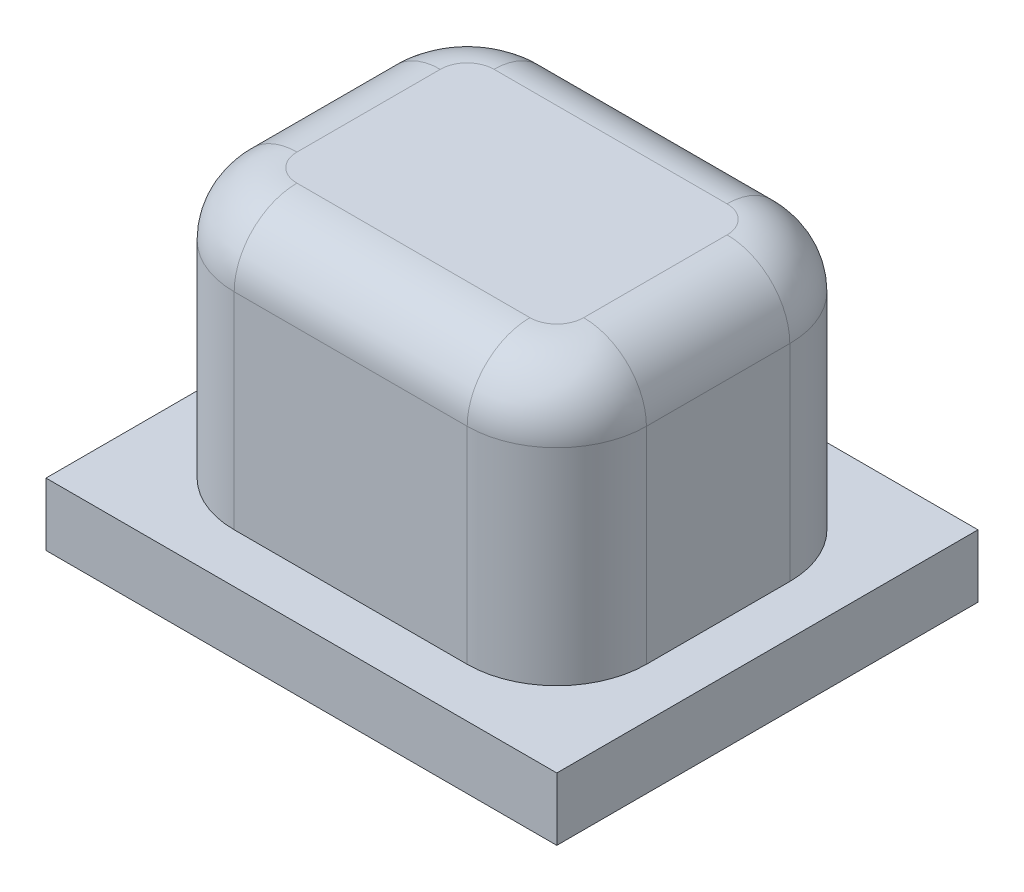
SolidWorks part; units mm, degrees
ref_plane "前视基准面" through (0, 0, 0) normal (0, 0, 1) x (1, 0, 0)
ref_plane "上视基准面" through (0, 0, 0) normal (0, 1, 0) x (1, 0, 0)
ref_plane "右视基准面" through (0, 0, 0) normal (1, 0, 0) x (0, 0, -1)
sketch "草图1" plane through (0, 0, 0) normal (0, 1, 0) x (1, 0, 0)
  line L1 (-1.3, -1.8) -> (1.3, -1.8)
  line L2 (-2.3, -0.8) -> (-2.3, 0.8)
  line L3 (-1.3, 1.8) -> (1.3, 1.8)
  line L4 (2.3, -0.8) -> (2.3, 0.8)
  line L5 (-2.3, -1.8) -> (2.3, 1.8) construction
  line L6 (-2.3, 1.8) -> (2.3, -1.8) construction
  arc A0 (1.3, -1.8) -> (2.3, -0.8) centre (1.3, -0.8) ccw
  arc A1 (-1.3, -1.8) -> (-2.3, -0.8) centre (-1.3, -0.8) cw
  arc A2 (1.3, 1.8) -> (2.3, 0.8) centre (1.3, 0.8) cw
  arc A3 (-2.3, 0.8) -> (-1.3, 1.8) centre (-1.3, 0.8) cw
  point P0 (0, 0)
  dimension "D3" = 1
  dimension "D1" = 4.6
  dimension "D2" = 3.6
extrude "按钮柱体" add sketch "草图1" along normal blind 3
sketch "草图2" plane through (0, 0, 0) normal (0, -1, 0) x (1, 0, 0)
  line L1 (-2.85, -2.35) -> (2.85, -2.35)
  line L2 (-2.85, -2.35) -> (-2.85, 2.35)
  line L3 (-2.85, 2.35) -> (2.85, 2.35)
  line L4 (2.85, -2.35) -> (2.85, 2.35)
  line L5 (-2.85, -2.35) -> (2.85, 2.35) construction
  line L6 (-2.85, 2.35) -> (2.85, -2.35) construction
  point P0 (0, 0)
  dimension "D1" = 5.7
  dimension "D2" = 4.7
extrude "按钮底座" add sketch "草图2" along normal blind 0.7
sketch "草图3" plane through (0, -0.7, 0) normal (0, -1, 0) x (1, 0, 0)
  line L5 (-1.75, -1.25) -> (1.75, -1.25)
  line L6 (-1.75, -1.25) -> (-1.75, 1.25)
  line L7 (-1.75, 1.25) -> (1.75, 1.25)
  line L8 (1.75, -1.25) -> (1.75, 1.25)
  line L9 (-1.75, -1.25) -> (1.75, 1.25) construction
  line L10 (-1.75, 1.25) -> (1.75, -1.25) construction
  point P0 (0, 0)
  dimension "D1" = 3.5
  dimension "D2" = 2.5
extrude "底部凹槽" cut sketch "草图3" against normal blind 2.7
fillet "圆角1" radius 0.7 8 edges at (2.0071, 3, -1.5071) (2.3, 3, 0) (2.0071, 3, 1.5071) (0, 3, 1.8) (-2.0071, 3, 1.5071) (-2.3, 3, 0) (-2.0071, 3, -1.5071) (0, 3, -1.8)
